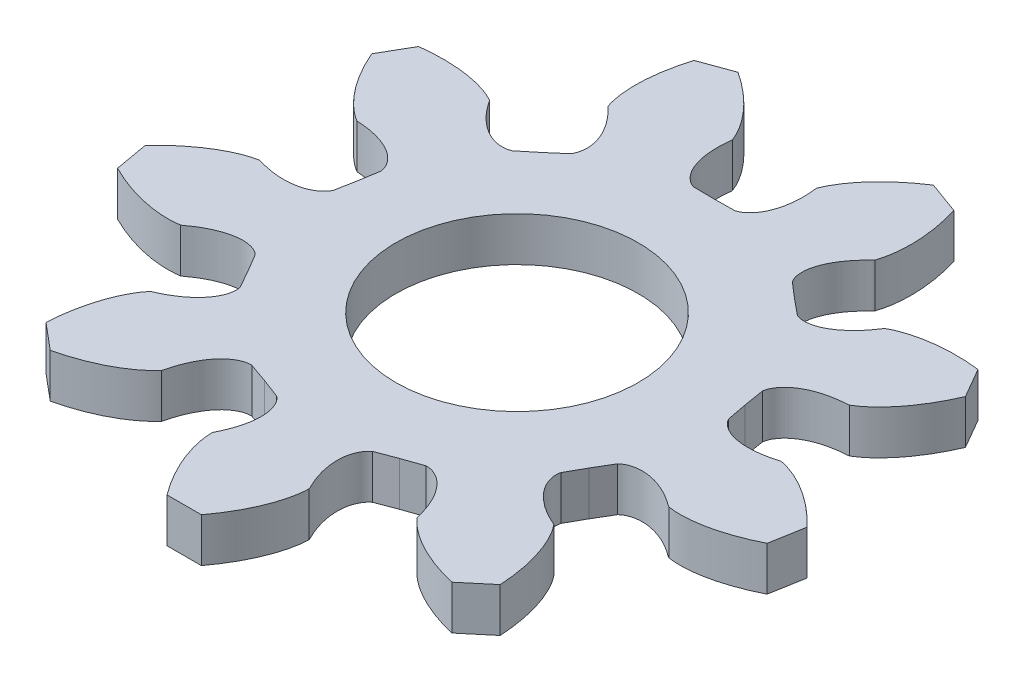
SolidWorks part; units mm, degrees
ref_plane "Plano frontal" through (0, 0, 0) normal (0, 0, 1) x (1, 0, 0)
ref_plane "Plano superior" through (0, 0, 0) normal (0, 1, 0) x (1, 0, 0)
ref_plane "Plano direito" through (0, 0, 0) normal (1, 0, 0) x (0, 0, -1)
sketch "Esboço1" plane through (0, 0, 0) normal (0, 1, 0) x (1, 0, 0)
  line L0 (-25.3837, 16.4538) -> (-26.9413, 13.7561)
  line L1 (-17.2988, 4.9706) -> (-17.6034, 3.104)
  line L2 (-17.6034, 3.104) -> (-17.9556, 1.2457)
  line L3 (-8.8688, 28.9207) -> (-11.796, 27.8553)
  line L4 (-30.0214, -3.712) -> (-29.4805, -6.7798)
  line L5 (-16.4467, -7.3117) -> (-15.4802, -8.9375)
  line L6 (-15.4802, -8.9375) -> (-14.5555, -10.5874)
  line L7 (-10.0566, 14.9272) -> (-11.4898, 13.6931)
  line L8 (-11.4898, 13.6931) -> (-12.9541, 12.4959)
  line L9 (11.796, 27.8553) -> (8.8688, 28.9207)
  line L10 (1.8912, 17.8991) -> (0, 17.875)
  line L11 (0, 17.875) -> (-1.8912, 17.8991)
  line L12 (26.9413, 13.7561) -> (25.3837, 16.4538)
  line L13 (12.9541, 12.4959) -> (11.4898, 13.693)
  line L14 (11.4898, 13.693) -> (10.0566, 14.9272)
  line L15 (29.4805, -6.7798) -> (30.0214, -3.712)
  line L16 (17.9556, 1.2457) -> (17.6034, 3.1039)
  line L17 (17.6034, 3.1039) -> (17.2988, 4.9706)
  line L18 (18.2254, -24.1433) -> (20.6117, -22.1409)
  line L19 (14.5555, -10.5874) -> (15.4802, -8.9375)
  line L20 (15.4802, -8.9375) -> (16.4467, -7.3117)
  line L21 (-1.5575, -30.2099) -> (1.5575, -30.2099)
  line L22 (4.3447, -17.4665) -> (6.1136, -16.797)
  line L23 (6.1136, -16.797) -> (7.899, -16.1728)
  line L24 (-20.6117, -22.1409) -> (-18.2254, -24.1433)
  line L25 (-7.899, -16.1728) -> (-6.1136, -16.797)
  line L26 (-6.1136, -16.797) -> (-4.3447, -17.4665)
  circle A0 centre (0, 0) radius 11
  spline S0 degree 3 number of poles 420 (-17.9564, 15.4545) -> (-25.3837, 16.4538)
  spline S1 degree 3 number of poles 364 (-12.9541, 12.4959) -> (-17.9564, 15.4545)
  spline S2 degree 3 number of poles 364 (-22.3622, 7.8235) -> (-17.2988, 4.9706)
  spline S3 degree 3 number of poles 420 (-26.9413, 13.7561) -> (-22.3622, 7.8235)
  spline S4 degree 3 number of poles 364 (-17.9556, 1.2457) -> (-23.6894, 0.2967)
  spline S5 degree 3 number of poles 420 (-23.6894, 0.2967) -> (-30.0214, -3.712)
  spline S6 degree 3 number of poles 420 (-29.4805, -6.7798) -> (-22.1593, -8.381)
  spline S7 degree 3 number of poles 364 (-22.1593, -8.381) -> (-16.4467, -7.3117)
  spline S8 degree 3 number of poles 420 (-3.8215, 23.381) -> (-8.8688, 28.9207)
  spline S9 degree 3 number of poles 364 (-1.8912, 17.8991) -> (-3.8215, 23.381)
  spline S10 degree 3 number of poles 364 (-12.1016, 20.3673) -> (-10.0566, 14.9272)
  spline S11 degree 3 number of poles 420 (-11.796, 27.8553) -> (-12.1016, 20.3673)
  spline S12 degree 3 number of poles 420 (12.1016, 20.3673) -> (11.796, 27.8553)
  spline S13 degree 3 number of poles 364 (10.0566, 14.9272) -> (12.1016, 20.3673)
  spline S14 degree 3 number of poles 364 (3.8215, 23.381) -> (1.8912, 17.8991)
  spline S15 degree 3 number of poles 420 (8.8688, 28.9207) -> (3.8215, 23.381)
  spline S16 degree 3 number of poles 420 (22.3622, 7.8235) -> (26.9413, 13.7561)
  spline S17 degree 3 number of poles 364 (17.2988, 4.9706) -> (22.3622, 7.8235)
  spline S18 degree 3 number of poles 364 (17.9564, 15.4545) -> (12.9541, 12.4959)
  spline S19 degree 3 number of poles 420 (25.3837, 16.4538) -> (17.9564, 15.4545)
  spline S20 degree 3 number of poles 420 (22.1593, -8.381) -> (29.4805, -6.7798)
  spline S21 degree 3 number of poles 364 (16.4467, -7.3117) -> (22.1593, -8.381)
  spline S22 degree 3 number of poles 364 (23.6894, 0.2967) -> (17.9556, 1.2457)
  spline S23 degree 3 number of poles 420 (30.0214, -3.712) -> (23.6894, 0.2967)
  spline S24 degree 3 number of poles 420 (11.5878, -20.6639) -> (18.2254, -24.1433)
  spline S25 degree 3 number of poles 364 (7.899, -16.1728) -> (11.5878, -20.6639)
  spline S26 degree 3 number of poles 364 (18.3378, -15) -> (14.5555, -10.5874)
  spline S27 degree 3 number of poles 420 (20.6117, -22.1409) -> (18.3378, -15)
  spline S28 degree 3 number of poles 420 (-4.4058, -23.278) -> (-1.5575, -30.2099)
  spline S29 degree 3 number of poles 364 (-4.3447, -17.4665) -> (-4.4058, -23.278)
  spline S30 degree 3 number of poles 364 (4.4058, -23.278) -> (4.3447, -17.4665)
  spline S31 degree 3 number of poles 420 (1.5575, -30.2099) -> (4.4058, -23.278)
  spline S32 degree 3 number of poles 420 (-18.3378, -15) -> (-20.6117, -22.1409)
  spline S33 degree 3 number of poles 364 (-14.5555, -10.5874) -> (-18.3378, -15)
  spline S34 degree 3 number of poles 364 (-11.5878, -20.6639) -> (-7.899, -16.1728)
  spline S35 degree 3 number of poles 420 (-18.2254, -24.1433) -> (-11.5878, -20.6639)
  point P76 (0, 0)
  dimension "D1" = 9
extrude "Ressalto-extrusão1" add sketch "Esboço1" along normal blind 4
